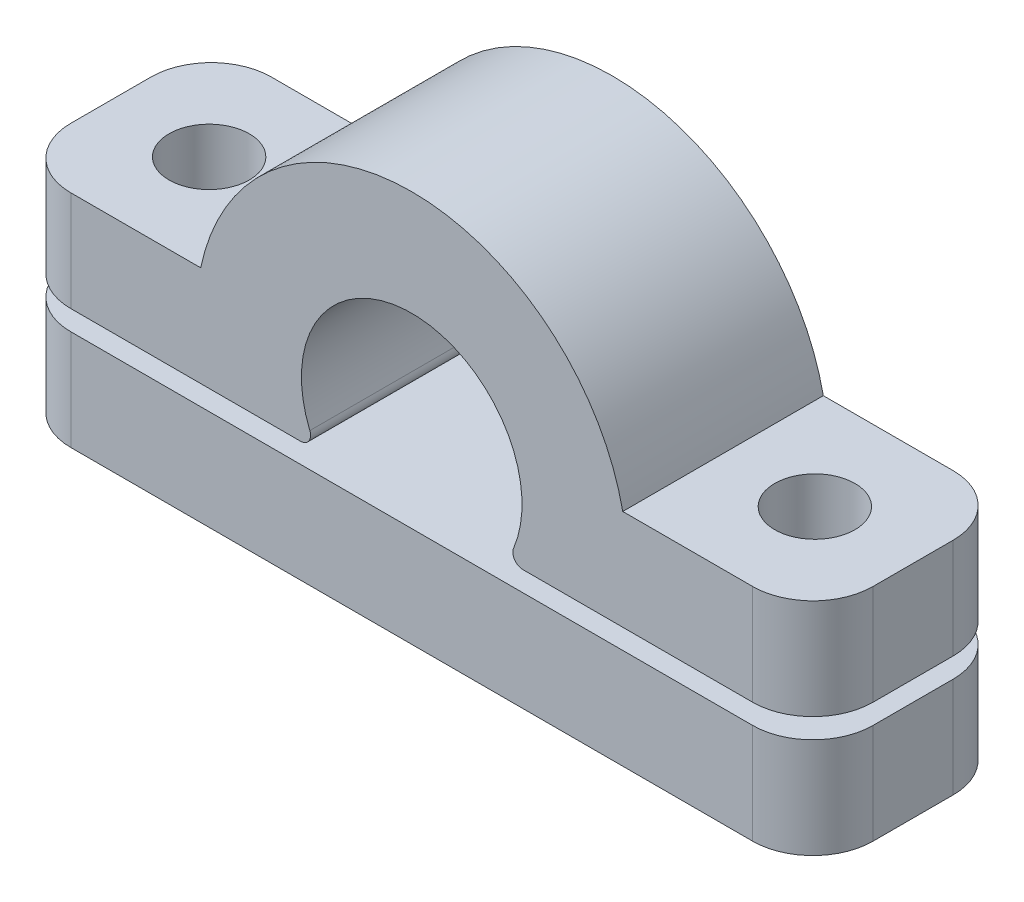
SolidWorks part; units mm, degrees
ref_plane "Front Plane" through (0, 0, 0) normal (0, 0, 1) x (1, 0, 0)
ref_plane "Top Plane" through (0, 0, 0) normal (0, 1, 0) x (1, 0, 0)
ref_plane "Right Plane" through (0, 0, 0) normal (1, 0, 0) x (0, 0, -1)
sketch "Sketch1" plane through (0, 0, 0) normal (0, 1, 0) x (1, 0, 0)
  line L1 (-20, 5) -> (20, 5)
  line L2 (-20, 5) -> (-20, -5)
  line L3 (-20, -5) -> (20, -5)
  line L4 (20, 5) -> (20, -5)
  line L5 (-20, 5) -> (20, -5) construction
  line L6 (-20, -5) -> (20, 5) construction
  point P0 (0, 0)
  dimension "D1" = 40
  dimension "D2" = 10
sketch "Sketch2" plane through (0, 0, 0) normal (0, 0, 1) x (1, 0, 0)
  line L0 (-4.7339, 0) -> (4.7339, 0) construction
  line L1 (0, -55) -> (0, 55) construction
  line L2 (-10.3789, 0) -> (10.3789, 0) construction
  line L3 (-10.3789, 0) -> (-4.7339, 0)
  line L4 (4.7339, 0) -> (10.3789, 0)
  arc A0 (-4.7339, 0) -> (4.7339, 0) centre (0, 2.8) cw
  arc A2 (-10.3789, 0) -> (10.3789, 0) centre (0, 2.8) cw
  point P3 (0, 2.8)
  point P4 (0, 0)
  point P5 (-4.7339, 0)
  point P6 (4.7339, 0)
  dimension "D4" = 10.75
  dimension "D1" = 2.8
  dimension "D2" = 5.5
  dimension "D3" = 5.5
extrude "Boss-Extrude1" add sketch "Sketch1" against normal blind 5 from offset 1 offset against normal yes
extrude "Boss-Extrude2" add sketch "Sketch2" along normal blind 5 and the other way blind 5
sketch "Sketch3" plane through (0, 0, 0) normal (0, 1, 0) x (1, 0, 0)
  line L0 (-10.75, -5) -> (10.75, -5) construction
  line L1 (-20, 5) -> (-10, 5)
  line L2 (-20, 5) -> (-20, -5)
  line L3 (-20, -5) -> (-10, -5)
  line L4 (-10, 5) -> (-10, -5)
  line L5 (0, -55) -> (0, 55) construction
  line L6 (20, -5) -> (10, -5)
  line L7 (20, 5) -> (20, -5)
  line L8 (20, 5) -> (10, 5)
  line L9 (10, 5) -> (10, -5)
  dimension "D1" = 10
extrude "Boss-Extrude3" add sketch "Sketch3" along normal blind 5
fillet "Fillet1" radius 3 4 edges at (20, 2.5, -5) (20, 2.5, 5) (-20, 2.5, -5) (-20, 2.5, 5)
fillet "Fillet2" radius 3 4 edges at (-20, -3.5, 5) (-20, -3.5, -5) (20, -3.5, 5) (20, -3.5, -5)
fillet "Fillet3" radius 0.5 2 edges at (-4.7339, 0, 0) (4.7339, 0, 0)
sketch "Sketch4" plane through (0, 0, 0) normal (0, 1, 0) x (1, 0, 0)
  line L0 (-55, 0) -> (55, 0) construction
  circle A0 centre (-15.1, 0) radius 2
  circle A1 centre (15.1, 0) radius 2
  dimension "D1" = 4
  dimension "D2" = 15.1
  dimension "D3" = 15.1
extrude "Cut-Extrude1" cut sketch "Sketch4" against normal through all both and the other way through all
equation "\"shaftDiameter\"= 10mm"
equation "\"holeDiameter\"= 4mm"
equation "\"D1@Sketch4\"=\"holeDiameter\""
